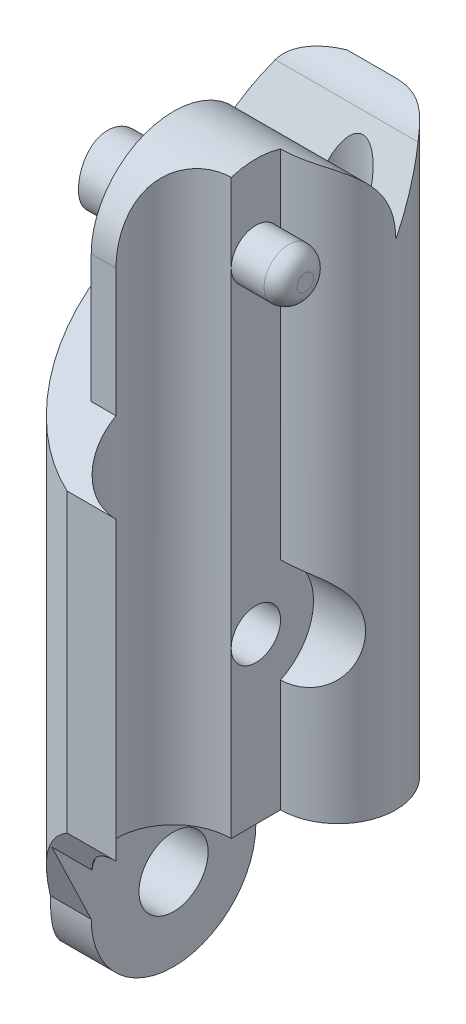
SolidWorks part; units mm, degrees
ref_plane "Front Plane" through (0, 0, 0) normal (0, 0, 1) x (1, 0, 0)
ref_plane "Top Plane" through (0, 0, 0) normal (0, 1, 0) x (1, 0, 0)
ref_plane "Right Plane" through (0, 0, 0) normal (1, 0, 0) x (0, 0, -1)
sketch "Sketch1" plane through (0, 0, 0) normal (0, 1, 0) x (1, 0, 0)
  line L0 (-2.958, 8.5) -> (2.958, 8.5)
  line L1 (-2.958, -8.5) -> (2.958, -8.5)
  arc A0 (-2.958, 8.5) -> (-2.958, -8.5) centre (0, 0) ccw
  arc A1 (2.958, 8.5) -> (2.958, -8.5) centre (0, 0) cw
  point P9 (-9, 0)
  point P10 (9, 0)
  dimension "D1" = 18
  dimension "D2" = 17
extrude "Boss-Extrude1" add sketch "Sketch1" along normal blind 45
sketch "Sketch2" plane through (0, 0, 0) normal (0, -1, 0) x (1, 0, 0)
  line L0 (-1.5, -5) -> (1.5, -5)
  line L1 (-1.5, 5) -> (1.5, 5)
  line L2 (0, -5) -> (0, 5) construction
  arc A2 (1.5, 5) -> (-1.5, 5) centre (0, 5) ccw
  arc A3 (1.5, -5) -> (-1.5, -5) centre (0, -5) cw
  dimension "D1" = 10
  dimension "D2" = 1.5
extrude "Cut-Extrude1" cut sketch "Sketch2" against normal blind 51.256
sketch "Sketch3" plane through (0, 0, -8.5) normal (0, 0, -1) x (-1, 0, 0)
  line L0 (5, 0) -> (5, 10)
  line L1 (5, 10) -> (-5, 10)
  line L2 (-5, 10) -> (-5, 0)
  line L3 (5, 0) -> (-5, 0)
  line L4 (-2.958, 0) -> (2.958, 0) construction
  point P10 (0, 0)
  dimension "D1" = 10
  dimension "D2" = 10
extrude "Cut-Extrude2" cut sketch "Sketch3" against normal up to surface (17 mm away) up to face at (0, 22.5, 8.5)
sketch "Sketch4" plane through (5, 0, 0) normal (-1, 0, 0) x (0, 0, 1)
  line L0 (-7.4833, 10) -> (-5, 5)
  line L1 (8.5, 12.3086) -> (5, 5)
  line L2 (7.4833, 0) -> (-7.4833, 0) construction
  line L3 (-7.4833, 10) -> (-9.8579, -1.8222)
  line L4 (-9.8579, -1.8222) -> (9.8579, -1.8222)
  line L6 (8.5, 45) -> (8.5, 10) construction
  line L7 (9.8579, -1.8222) -> (8.5, 12.3086)
  arc A0 (-5, 5) -> (5, 5) centre (0, 5) ccw
  circle A1 centre (0, 5) radius 2.1
  point P7 (0, 0)
  dimension "D1" = 4.2
  dimension "D2" = 5
  dimension "D3" = 12.0584
  dimension "D4" = 37.769
extrude "Cut-Extrude3" cut sketch "Sketch4" against normal mid plane 35
ref_plane "Plane1" through (-2.958, 0, 0) normal (-1, 0, 0) x (0, 0, 1)
sketch "Sketch6" plane through (-2.958, 0, 0) normal (-1, 0, 0) x (0, 0, 1)
  line L0 (8.5, 30.2956) -> (0, 35)
  line L1 (8.5, 45) -> (8.5, 12.3086) construction
  line L3 (8.5, 45) -> (-8.5, 45) construction
  line L4 (8.5, 30.2956) -> (18.3464, 50.6263)
  line L7 (-8.5, 45) -> (18.3464, 50.6263)
  line L8 (8.5, 45) -> (8.5, 12.3086) construction
  line L12 (-5, 40) -> (-6.926, 43.8779)
  line L13 (-5, 5) -> (-7.4833, 10) construction
  arc A0 (0, 35) -> (-5, 40) centre (0, 40) cw
  circle A1 centre (0, 40) radius 2
  arc A3 (-6.926, 43.8779) -> (-8.5, 45) centre (-8.7637, 42.9652) ccw
  dimension "D1" = 5
  dimension "D3" = 4
  dimension "D2" = 5
  dimension "D4" = 8.5
extrude "Cut-Extrude5" cut sketch "Sketch6" against normal blind 9.6 from surface starting at face at (5, 7.1, 0)
sketch "Sketch7" plane through (5, 0, 0) normal (1, 0, 0) x (0, 0, -1)
  line L3 (-8.5, 45) -> (-8.5, 12.3086) construction
  line L4 (-5, 40) -> (-5, 32.2327)
  line L5 (-7.4833, 45) -> (7.4833, 45) construction
  line L6 (-5, 32.2327) -> (-8.5, 30.2956)
  line L8 (0, 35) -> (-7.4833, 30.8583) construction
  line L10 (8.5, 45) -> (18.9606, 55.6302)
  line L11 (18.9606, 55.6302) -> (-10.6436, 58.7694)
  line L12 (-10.6436, 58.7694) -> (-8.5, 30.2956)
  line L14 (8.5, 45) -> (8.5, 10) construction
  line L15 (5, 40) -> (6.926, 43.8779)
  arc A0 (5, 40) -> (-5, 40) centre (0, 40) ccw
  arc A4 (6.926, 43.8779) -> (8.5, 45) centre (8.7637, 42.9652) cw
  dimension "D1" = 5
fillet "Fillet3" radius 1 4 edges at (0, 10, 6.5) (0, 10, 5) (0, 10, -6.5) (0, 10, -5)
extrude "Cut-Extrude6" cut sketch "Sketch6<3>" along normal blind 6.604 from surface starting at face at (-5, 2.9, 0)
sketch "Sketch6<3>" plane through (-2.958, 0, 0) normal (-1, 0, 0) x (0, 0, 1) same geometry as "Sketch6"
extrude "Cut-Extrude7" cut sketch "Sketch7" against normal blind 14.986
sketch "Sketch8" plane through (0, 10, 0) normal (0, -1, 0) x (1, 0, 0)
  line L0 (0, -1.5) -> (0, 1.5)
  line L1 (-2.958, -8.5) -> (2.958, -8.5) construction
  line L2 (2.958, 8.5) -> (-2.958, 8.5) construction
  line L3 (0, -8.5) -> (17.548, -23.9281)
  line L4 (17.548, -23.9281) -> (17.548, 21.762)
  line L5 (17.548, 21.762) -> (0, 8.5)
  arc A0 (0, -1.5) -> (0, -8.5) centre (0, -5) cw
  arc A1 (0, 1.5) -> (0, 8.5) centre (0, 5) cw
  arc A4 (-2.2913, -4) -> (2.2913, -4) centre (0, -5) ccw construction
  arc A5 (-0.7187, 7.3945) -> (-2.2913, 4) centre (0, 5) ccw construction
extrude "Cut-Extrude8" cut sketch "Sketch8" against normal mid plane 78.0815
sketch "Sketch9" plane through (0, 0, 0) normal (1, 0, 0) x (0, 0, -1)
  line L0 (1.5, 10) -> (-1.5, 10) construction
  line L1 (0, 20) -> (0, 10) construction
  circle A0 centre (0, 20) radius 1.5
  dimension "D1" = 3
  dimension "D2" = 10
extrude "Cut-Extrude9" cut sketch "Sketch9" against normal blind 11.2795
sketch "Sketch10" plane through (0, 0, 0) normal (1, 0, 0) x (0, 0, -1)
  circle A0 centre (0, 20) radius 2.75
  dimension "D1" = 5.5
extrude "Cut-Extrude11" cut sketch "Sketch10" against normal blind 4.778 from offset 5.5 offset against normal yes
sketch "Sketch12" plane through (0, 0, 0) normal (1, 0, 0) x (0, 0, -1)
  line L0 (-1.5, 44.7697) -> (-1.5, 20) construction
  circle A0 centre (0, 40) radius 1.5
  circle A1 centre (0, 40) radius 2 construction
extrude "Boss-Extrude2" add sketch "Sketch12" along normal blind 3
fillet "Fillet6" radius 1 1 edges at (3, 40, -1.5)
sketch "Sketch13" plane through (0, 0, 0) normal (1, 0, 0) x (0, 0, -1)
  line L1 (0, 16.5) -> (0, 23.5)
  arc A0 (0, 16.5) -> (0, 23.5) centre (0, 20) ccw
  arc A1 (1.5, 20) -> (-1.5, 20) centre (0, 20) ccw construction
  dimension "D1" = 3.5
extrude "Cut-Extrude12" cut sketch "Sketch13" along normal blind 11.684
